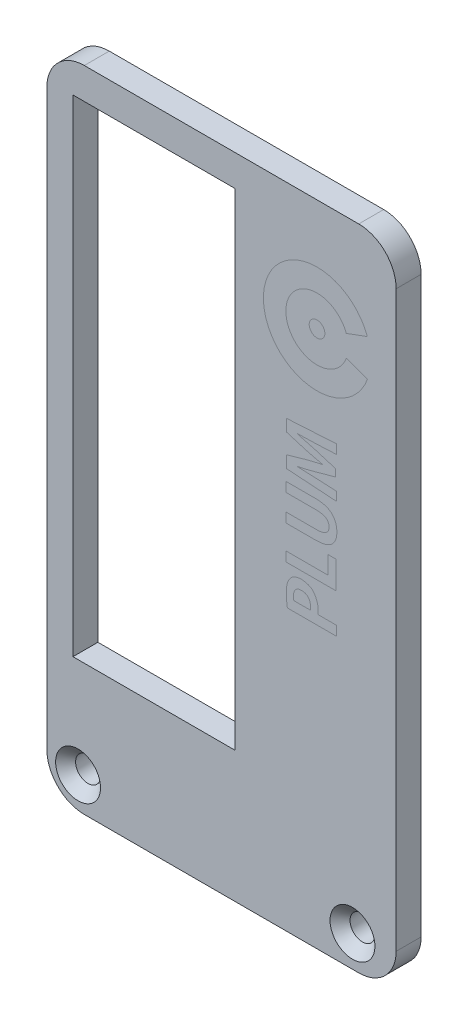
SolidWorks part; units mm, degrees
ref_plane "前视基准面" through (0, 0, 0) normal (0, 0, 1) x (1, 0, 0)
ref_plane "上视基准面" through (0, 0, 0) normal (0, 1, 0) x (1, 0, 0)
ref_plane "右视基准面" through (0, 0, 0) normal (1, 0, 0) x (0, 0, -1)
other "Configuration Table"
sketch "草图1" plane through (0, 0, 0) normal (0, 0, 1) x (1, 0, 0)
  line L1 (-14, -26) -> (14, -26)
  line L2 (-14, -26) -> (-14, 26)
  line L3 (-14, 26) -> (14, 26)
  line L4 (14, -26) -> (14, 26)
  line L5 (-14, -26) -> (14, 26) construction
  line L6 (-14, 26) -> (14, -26) construction
  point P0 (0, 0)
  dimension "D1" = 28
  dimension "D2" = 52
extrude "凸台-拉伸1" add sketch "草图1" along normal blind 2
sketch "草图2" plane through (0, 0, 2) normal (0, 0, 1) x (1, 0, 0)
  line L0 (-14, -26) -> (14, -26) construction
  line L1 (-14, 26) -> (-14, -26) construction
  circle A0 centre (-11.5, -23.5) radius 1
  circle A1 centre (10.5, -23.5) radius 1
  point P6 (-12.7871, -24.4553)
  dimension "D2" = 2.5
  dimension "D3" = 2.5
  dimension "D4" = 2
  dimension "D5" = 2
  dimension "D1" = 22
extrude "切除-拉伸1" cut sketch "草图2" against normal blind 2
sketch "草图3" plane through (0, 0, 2) normal (0, 0, 1) x (1, 0, 0)
  line L1 (-11.9105, -15.5) -> (1.0895, -15.5)
  line L2 (-11.9105, -15.5) -> (-11.9105, 23.5)
  line L3 (-11.9105, 23.5) -> (1.0895, 23.5)
  line L4 (1.0895, -15.5) -> (1.0895, 23.5)
  circle A0 centre (-11.5, -23.5) radius 1 construction
  dimension "D1" = 8
  dimension "D2" = 13
  dimension "D3" = 39
extrude "切除-拉伸2" cut sketch "草图3" against normal blind 2
fillet "圆角1" radius 3 4 edges at (-14, -26, 1) (14, -26, 1) (14, 26, 1) (-14, 26, 1)
chamfer "倒角1" distance 0.8 angle 45 2 edges at (-10.5, -23.5, 2) (11.5, -23.5, 2)
sketch "草图4" plane through (0, 0, 2) normal (0, 0, 1) x (1, 0, 0)
  line L0 (10.0019, 17.9012) -> (11.6905, 18.5244)
  line L1 (10.0095, 16.1911) -> (11.7037, 15.5831)
  arc A0 (10.0019, 17.9012) -> (10.0095, 16.1911) centre (7.6565, 17.0357) ccw
  arc A1 (11.6905, 18.5244) -> (11.7037, 15.5831) centre (7.6565, 17.0357) ccw
  point P3 (11.3154, 18.6788)
  point P6 (11.0066, 18.882)
  dimension "D1" = 1.8
  dimension "D2" = 5
  dimension "D3" = 40
extrude "切除-拉伸3" cut sketch "草图4" against normal blind 2
sketch "草图5" plane through (0, 0, 2) normal (0, 0, 1) x (1, 0, 0)
  line L0 (11.7037, 15.5831) -> (10.0095, 16.1911) construction
  line L1 (10.0019, 17.9012) -> (11.6905, 18.5244) construction
  line L2 (11.7037, 15.5831) -> (10.0095, 16.1911)
  line L3 (10.0019, 17.9012) -> (11.6905, 18.5244)
  arc A0 (10.0019, 17.9012) -> (10.0095, 16.1911) centre (7.6565, 17.0357) ccw construction
  arc A1 (11.6905, 18.5244) -> (11.7037, 15.5831) centre (7.6565, 17.0357) ccw construction
  arc A2 (10.0019, 17.9012) -> (10.0095, 16.1911) centre (7.6565, 17.0357) ccw
  arc A3 (11.6905, 18.5244) -> (11.7037, 15.5831) centre (7.6565, 17.0357) ccw
extrude "凸台-拉伸2" add sketch "草图5" against normal blind 2 separate body
sketch "草图6" plane through (0, 0, 2) normal (0, 0, 1) x (1, 0, 0)
  circle A0 centre (7.6565, 17.0357) radius 0.6269
extrude "切除-拉伸4" cut sketch "草图6" against normal blind 2
extrude "凸台-拉伸4" add sketch "草图6<3>" against normal blind 2 separate body
sketch "草图6<3>" plane through (0, 0, 2) normal (0, 0, 1) x (1, 0, 0) same geometry as "草图6"
sketch "草图7" plane through (0, 0, 2) normal (0, 0, 1) x (1, 0, 0)
  line L1 (9.1997, -3.9103) -> (9.1997, 9.396) construction
  text T0 "PLUM" font "@Adobe Gothic Std B" height 4
  point P3 (0, 0)
  point P4 (10.1417, -4.0319)
  point P5 (9.1997, -3.9103)
  point P6 (0, 0)
  point P7 (0, 0)
extrude "切除-拉伸7" cut sketch "草图7" against normal blind 2
extrude "凸台-拉伸5" add sketch "草图7<2>" against normal blind 2 separate body
sketch "草图7<2>" plane through (0, 0, 2) normal (0, 0, 1) x (1, 0, 0) same geometry as "草图7"
